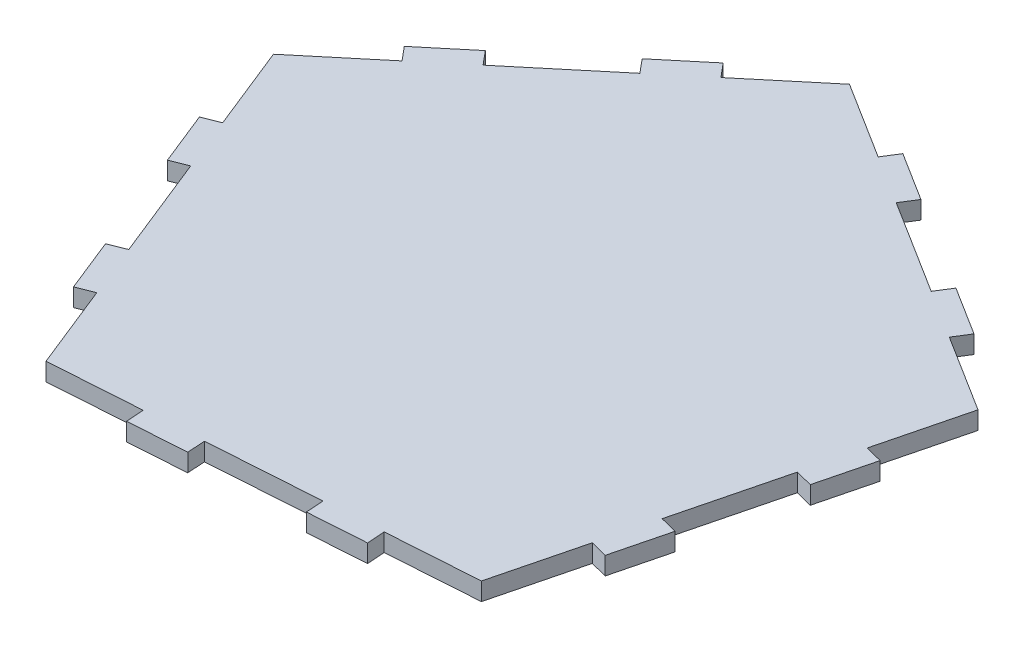
SolidWorks part; units mm, degrees
ref_plane "Front Plane" through (0, 0, 0) normal (0, 0, 1) x (1, 0, 0)
ref_plane "Top Plane" through (0, 0, 0) normal (0, 1, 0) x (1, 0, 0)
ref_plane "Right Plane" through (0, 0, 0) normal (1, 0, 0) x (0, 0, -1)
sketch "Sketch1" plane through (0, 0, 0) normal (0, 1, 0) x (1, 0, 0)
  line L1 (-59.9258, 15.1181) -> (-32.8962, -52.3211)
  line L2 (-32.8962, -52.3211) -> (39.5948, -47.4543)
  line L3 (39.5948, -47.4543) -> (57.3672, 22.9927)
  line L4 (57.3672, 22.9927) -> (-4.14, 61.6646)
  line L5 (-4.14, 61.6646) -> (-59.9258, 15.1181)
  circle A0 centre (0, 0) radius 50 construction
  dimension "D1" = 100
extrude "Boss-Extrude1" add sketch "Sketch1" along normal blind 3.18
ref_axis "Axis" through (0, 3.339, 0) along (0, -1, 0)
sketch "Axis Check" plane through (0, 3.18, 0) normal (0, 1, 0) x (1, 0, 0)
  line L0 (3.3493, -49.8877) -> (-4.14, 61.6646) construction
  line L1 (-32.8962, -52.3211) -> (39.5948, -47.4543) construction
  line L2 (57.3672, 22.9927) -> (-46.411, -18.6015) construction
  line L3 (-59.9258, 15.1181) -> (-32.8962, -52.3211) construction
  line L4 (-32.0329, 38.3913) -> (39.5948, -47.4543) construction
  line L5 (-4.14, 61.6646) -> (-59.9258, 15.1181) construction
  line L6 (-59.9258, 15.1181) -> (48.481, -12.2308) construction
  line L7 (39.5948, -47.4543) -> (57.3672, 22.9927) construction
  line L8 (-32.8962, -52.3211) -> (26.6136, 42.3287) construction
  line L9 (57.3672, 22.9927) -> (-4.14, 61.6646) construction
sketch "Sketch2" plane through (0, 0, 0) normal (0, -1, 0) x (1, 0, 0)
  line L0 (-53.8107, 0.1392) -> (-50.859, -1.0438)
  line L1 (-53.8107, 0.1392) -> (-50.1723, 9.2172)
  line L2 (-50.859, -1.0438) -> (-47.2205, 8.0342)
  line L3 (-50.1723, 9.2172) -> (-47.2205, 8.0342)
  line L4 (-59.9258, -15.1181) -> (-32.8962, 52.3211) construction
  line L5 (-42.6498, 27.9858) -> (-39.0113, 37.0638)
  line L6 (-42.6498, 27.9858) -> (-39.6981, 26.8028)
  line L7 (-39.0113, 37.0638) -> (-36.0596, 35.8808)
  line L8 (-39.6981, 26.8028) -> (-36.0596, 35.8808)
  line L9 (-46.411, 18.6015) -> (-19.2439, 7.7129) construction
  line L10 (-40.8306, 32.5248) -> (-37.8788, 31.3418) construction
  dimension "D1" = 3.18
  dimension "D2" = 9.78
  dimension "D3" = 10.11
extrude "Cut F" [suppressed] cut sketch "Sketch2" against normal through all
sketch "Sketch4" [suppressed] plane through (0, 3.18, 0) normal (0, 1, 0) x (1, 0, 0)
  line L9 (26.6136, 42.3287) -> (-26.6136, -42.3287) construction
  line L10 (57.3672, 22.9927) -> (-4.14, 61.6646) construction
  line L11 (-27.7286, -6.3206) -> (-6.3206, 27.7286)
  line L12 (-27.7286, -6.3206) -> (6.3206, -27.7286)
  line L13 (-6.3206, 27.7286) -> (27.7286, 6.3206)
  line L14 (6.3206, -27.7286) -> (27.7286, 6.3206)
  line L15 (-27.7286, -6.3206) -> (27.7286, 6.3206) construction
  line L16 (-6.3206, 27.7286) -> (6.3206, -27.7286) construction
  line L20 (0, 0) -> (39.0006, -24.5211) construction
  circle A0 centre (-14.9622, -23.7972) radius 3.25
  circle A1 centre (23.7972, -14.9622) radius 3.25
  point P5 (0, 0)
  point P6 (-14.9622, -23.7972)
  dimension "D3" = 6.5
  dimension "D1" = 40.22
  dimension "D2" = 40.22
  dimension "D4" = 8
  dimension "D5" = 8
extrude "Top Cut" [suppressed] cut sketch "Sketch4" against normal blind 10
sketch "Sketch7" [suppressed] plane through (0, 3.18, 0) normal (0, 1, 0) x (1, 0, 0)
  line L0 (0, 0) -> (26.6136, 42.3287) construction
  line L1 (57.3672, 22.9927) -> (-4.14, 61.6646) construction
  line L2 (1.0645, 1.6931) -> (-22.7326, 16.6553) construction
  line L3 (-6.1086, 1.4782) -> (-24.8617, 13.269) construction
  line L5 (-6.3206, 27.7286) -> (-27.7286, -6.3206) construction
  circle A0 centre (-22.7326, 16.6553) radius 1
  circle A1 centre (-24.8617, 13.269) radius 1
  dimension "D5" = 2
  dimension "D1" = 4
  dimension "D2" = 2
  dimension "D3" = 8
  dimension "D4" = 8
extrude "Top Cut 2" [suppressed] cut sketch "Sketch7" against normal through all
sketch "Bottom Cut" plane through (0, 3.18, 0) normal (0, 1, 0) x (1, 0, 0)
  line L0 (-32.0329, 38.3913) -> (39.5948, -47.4543) construction
  line L1 (-4.14, 61.6646) -> (-59.9258, 15.1181) construction
  circle A0 centre (-7.1981, 30.4014) radius 1.6
  circle A1 centre (-28.6205, 12.5271) radius 1.6
  circle A2 centre (-4.5697, -32.2189) radius 1.6
  circle A3 centre (32.5163, -1.2751) radius 1.6
  point P13 (0, 0)
  point P14 (0, 0)
  point P15 (0, 0)
  point P16 (0, 0)
  point P17 (-28.6205, 12.5271)
  dimension "D1" = 3.2
  dimension "D2" = 27.9
  dimension "D3" = 48.3
  dimension "D4" = 50.8
sketch "Sketch3" plane through (0, 3.18, 0) normal (0, 1, 0) x (1, 0, 0)
  line L0 (0, 0) -> (-40.9819, 49.1167) construction
  line L1 (-49.5112, 27.9494) -> (-45.4366, 23.066)
  line L3 (-45.4366, 23.066) -> (-37.5894, 29.6135)
  line L4 (-41.664, 34.4969) -> (-37.5894, 29.6135)
  line L5 (-4.14, 61.6646) -> (-59.9258, 15.1181) construction
  line L6 (-71.9961, 5.0469) -> (-69.9588, 2.6052)
  line L7 (-71.9961, 5.0469) -> (-47.4739, 25.5077)
  line L14 (-26.4764, 47.1691) -> (-22.4018, 42.2857)
  line L16 (-22.4018, 42.2857) -> (-14.5546, 48.8333)
  line L17 (-18.6292, 53.7166) -> (-14.5546, 48.8333)
  line L18 (-42.539, 27.5695) -> (-41.513, 26.3398) construction
  line L19 (-49.5112, 27.9494) -> (-41.664, 34.4969)
  line L21 (-26.4764, 47.1691) -> (-18.6292, 53.7166)
  line L22 (-16.5919, 51.275) -> (4.7866, 69.1127)
  line L23 (-39.6267, 32.0552) -> (-24.4391, 44.7274)
  line M18 (-4.14, 61.6646) -> (-59.9258, 15.1181)
  dimension "D1" = 3.18
  dimension "D2" = 10.22
  dimension "D3" = 9.89
  dimension "D4" = 100
extrude "Extrude M" add sketch "Sketch3" against normal up to surface (3.18 mm away) contours L21 L14 L7 L17 | L19 L1 L4 M18 region at (-44.5689, 3.18, -30.0023) region at (-21.5341, 3.18, -49.222) up to face at (0, 0, 0)
pattern_circular "Circle F" [suppressed] count 5 over 360 about axis through (0, 3.339, 0) along (0, -1, 0) of bodies 173
pattern_circular "Circle M" count 5 over 360 about axis through (0, 3.339, 0) along (0, -1, 0) of "Extrude M"
pattern_circular "Circle Side F" [suppressed] count 5 over 360 about axis through (0, 3.339, 0) along (0, -1, 0) of bodies 173
pattern_circular "Circle Side M" [suppressed] count 5 over 360 about axis through (0, 3.339, 0) along (0, -1, 0) of bodies 168
equation "\"kerf\"= .22mm"
equation "\"tabWidthF\"= 10 - \"kerf\""
equation "\"tabThickness\"= 3.18"
equation "\"D1@Sketch2\"=\"tabThickness\""
equation "\"tabWidthM\"= 10 + \"kerf\""
equation "\"halfkerf\"= \"kerf\" / 2.00mm"
equation "\"tabLength\" = \"kerf\" + 12"
